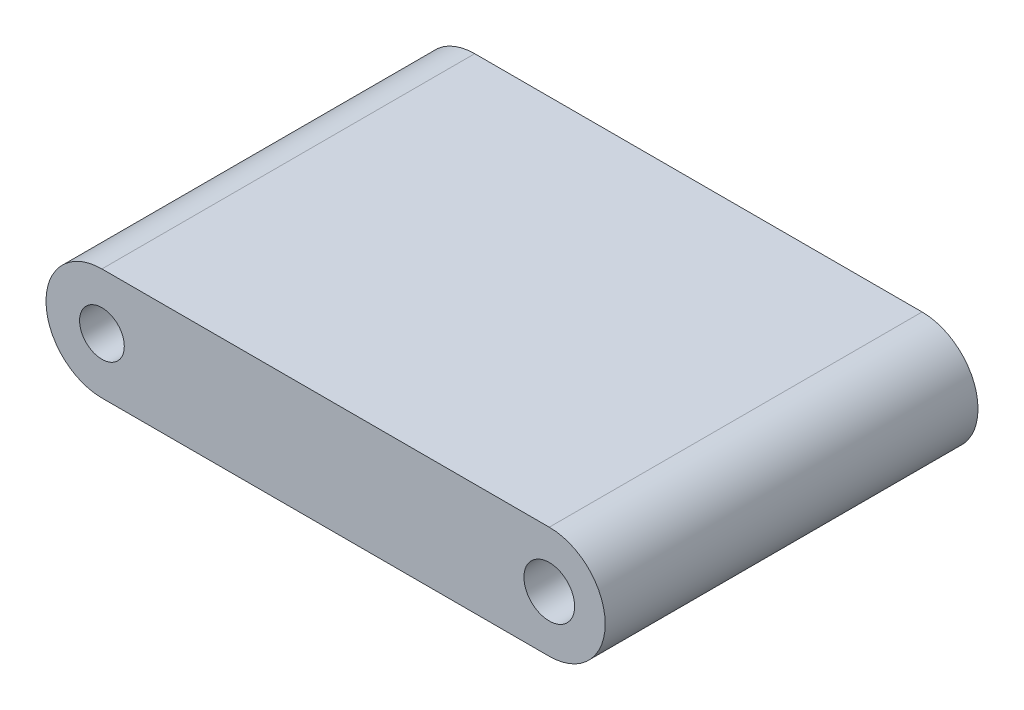
SolidWorks part; units mm, degrees
ref_plane "Front Plane" through (0, 0, 0) normal (0, 0, 1) x (1, 0, 0)
ref_plane "Top Plane" through (0, 0, 0) normal (0, 1, 0) x (1, 0, 0)
ref_plane "Right Plane" through (0, 0, 0) normal (1, 0, 0) x (0, 0, -1)
sketch "Sketch1" plane through (0, 0, 0) normal (0, 0, 1) x (1, 0, 0)
  line L0 (0, 0) -> (38.1, 0) construction
  line L1 (0, 4.7625) -> (38.1, 4.7625)
  line L2 (0, -4.7625) -> (38.1, -4.7625)
  arc A0 (0, 4.7625) -> (0, -4.7625) centre (0, 0) ccw
  arc A1 (38.1, -4.7625) -> (38.1, 4.7625) centre (38.1, 0) ccw
  circle A2 centre (0, 0) radius 1.905
  circle A3 centre (38.1, 0) radius 2.159
  point P3 (19.05, 0)
  dimension "D3" = 3.81
  dimension "D4" = 4.318
  dimension "D1" = 9.525
  dimension "D2" = 38.1
extrude "Boss-Extrude1" add sketch "Sketch1" along normal blind 31.75
